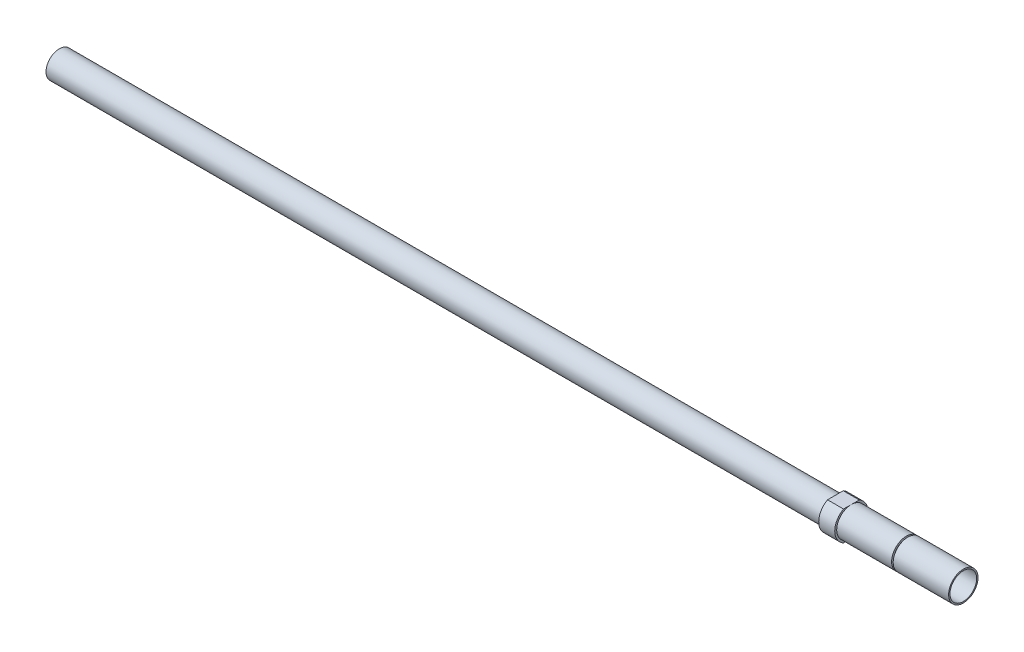
SolidWorks part; units mm, degrees
ref_plane "XY" through (0, 0, 0) normal (0, 0, 1) x (1, 0, 0)
ref_plane "XZ" through (0, 0, 0) normal (0, 1, 0) x (1, 0, 0)
ref_plane "YZ" through (0, 0, 0) normal (1, 0, 0) x (0, 0, -1)
ref_axis "X" through (-226.1616, 0, 0) along (1, 0, 0)
ref_axis "Y" through (0, -3.85, 0) along (0, 1, 0)
ref_axis "Z" through (0, 0, 4.3656) along (0, 0, -1)
sketch "Sketch1" plane through (0, 0, 0) normal (0, 0, 1) x (1, 0, 0)
  line L0 (0, 0) -> (-215.392, 0)
  line L1 (-215.392, 0) -> (-215.392, 3.175)
  line L2 (-215.392, 3.175) -> (-30.48, 3.175)
  line L3 (-30.48, 3.175) -> (-30.48, 3.9687)
  line L4 (-30.48, 3.9687) -> (-26.67, 3.9687)
  line L5 (-26.67, 3.9687) -> (-26.67, 3.5)
  line L6 (-26.67, 3.5) -> (-13.589, 3.5)
  line L7 (0, 3.5) -> (0, 0)
  line L8 (-13.589, 3.5) -> (-13.589, 3.0226)
  line L9 (-13.589, 3.0226) -> (-13.208, 3.0226)
  line L10 (-13.208, 3.0226) -> (-13.208, 3.5)
  line L11 (-13.208, 3.5) -> (0, 3.5)
  dimension "D1" = 184.912
  dimension "D2" = 3.81
  dimension "D3" = 13.081
  dimension "D4" = 3.175
  dimension "D5" = 3.9688
  dimension "D6" = 3.0226
  dimension "D7" = 0.381
  dimension "D8" = 30.48
  dimension "D9" = 3.5
revolve "Revolve1" add sketch "Sketch1" angle 360 about L0
sketch "Sketch2" plane through (0, 0, 0) normal (1, 0, 0) x (0, 0, -1)
  line L1 (-3.9687, -3.5) -> (3.9687, -3.5)
  line L2 (-3.9687, -3.5) -> (-3.9687, 3.5)
  line L3 (-3.9687, 3.5) -> (3.9687, 3.5)
  line L4 (3.9687, -3.5) -> (3.9687, 3.5)
  circle A0 centre (0, 0) radius 3.5 construction
  circle A1 centre (0, 0) radius 3.9687 construction
extrude "Cut-Extrude1" cut sketch "Sketch2" against normal through all flip side to cut
sketch "Sketch3" plane through (-30.48, 0, 0) normal (-1, 0, 0) x (0, 0, 1)
  circle A0 centre (0, 0) radius 3.175
  circle A1 centre (0, 0) radius 3.175 construction
extrude "Cut-Extrude2" cut sketch "Sketch3" against normal through all from offset 17.78 offset against normal yes
